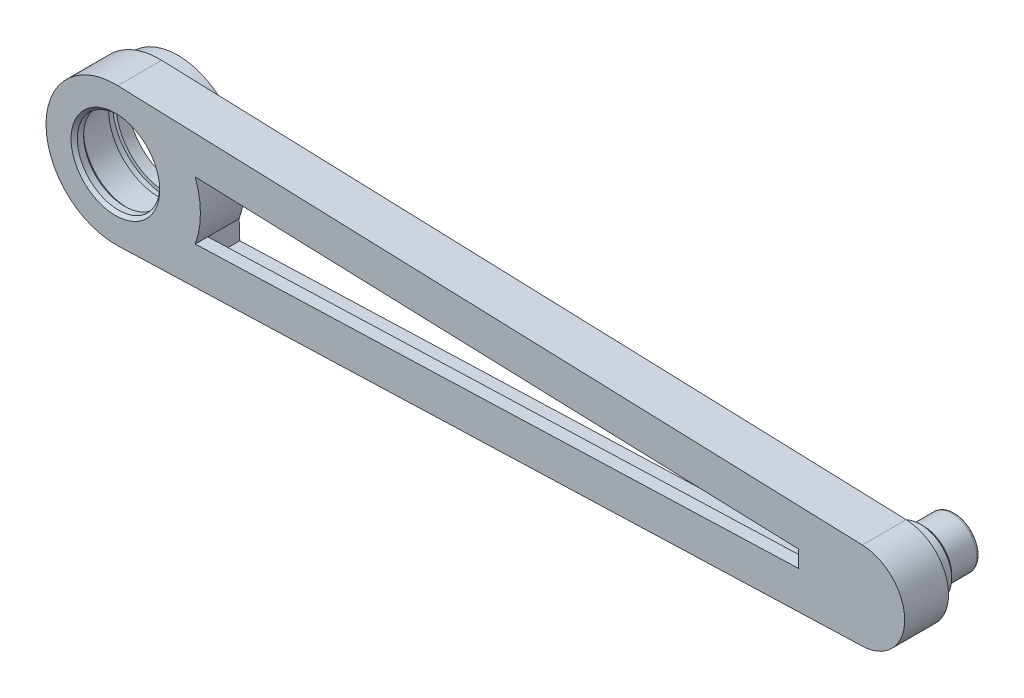
SolidWorks part; units mm, degrees
material "PEI"
ref_plane "前视基准面" through (0, 0, 0) normal (0, 0, 1) x (1, 0, 0)
ref_plane "上视基准面" through (0, 0, 0) normal (0, 1, 0) x (1, 0, 0)
ref_plane "右视基准面" through (0, 0, 0) normal (1, 0, 0) x (0, 0, -1)
other "Configuration Table"
sketch "草图1" plane through (0, 0, 0) normal (0, 0, 1) x (1, 0, 0)
  line L0 (0, 0) -> (119, 0) construction
  line L1 (0.3792, 11.0685) -> (119.2397, 6.9959)
  line L2 (0.3796, -11.0685) -> (119, -7)
  circle A0 centre (119, 0) radius 7
  circle A1 centre (0, 0) radius 8.075
  circle A2 centre (0, 0) radius 11.075
  dimension "D1" = 16.15
  dimension "D3" = 14
  dimension "D2" = 3
  dimension "D4" = 119
extrude "凸台-拉伸1" add sketch "草图1" along normal blind 7 contours A1 A2 | A2 L0 A0 L1 | L0 A2 L2 A0 | A0 region at (7.739, -7.4781, 0) region at (57.6854, 4.654, 0) region at (57.6797, -4.6531, 0) region at (114.2733, 4.8914, 0)
sketch "草图2" plane through (0, 0, 7) normal (0, 0, 1) x (1, 0, 0)
  circle A0 centre (0, 0) radius 8.075 construction
  circle A1 centre (0, 0) radius 8.075
  circle A2 centre (0, 0) radius 6.575
  dimension "D1" = 1.5
extrude "凸台-拉伸2" add sketch "草图2" against normal blind 2
sketch "草图3" plane through (0, 0, 0) normal (0, 0, -1) x (-1, 0, 0)
  arc A0 (-119.2397, 6.9959) -> (-119, -7) centre (-119, 0) ccw construction
  arc A1 (-119.2397, 6.9959) -> (-119, -7) centre (-119, 0) ccw
  circle A2 centre (-119, 0) radius 4
  dimension "D1" = 8
extrude "凸台-拉伸3" add sketch "草图3" along normal blind 10 contours A2 region at (119, 0, 0)
sketch "草图4" plane through (0, 0, 0) normal (0, 0, -1) x (-1, 0, 0)
  circle A0 centre (-119, 0) radius 4 construction
  circle A1 centre (-119, 0) radius 4
  circle A2 centre (-119, 0) radius 5
  dimension "D1" = 1
extrude "凸台-拉伸4" add sketch "草图4" along normal blind 3
chamfer "倒角1" distance 0.5 angle 45 4 edges at (6.575, 0, 7) (6.575, 0, 5) (114, 0, -3) (115, 0, -10)
chamfer "倒角2" [suppressed] distance 1 angle 45
sketch "草图5" plane through (0, 0, 0) normal (0, 0, -1) x (-1, 0, 0)
  line L0 (-0.1738, 5.072) -> (-119.0901, 0.9975)
  line L1 (-118.9996, -0.9965) -> (-0.174, -5.072)
  line L2 (-119, -7) -> (-0.3796, -11.0685)
  line L3 (-119, -7) -> (-0.3796, -11.0685)
  line L8 (-0.3792, 11.0685) -> (-119.2397, 6.9959)
  line L9 (-0.3792, 11.0685) -> (-119.2397, 6.9959)
  arc A0 (-119.0901, 0.9975) -> (-118.9996, -0.9965) centre (-119.0945, -0.0017) ccw
  arc A1 (-0.174, -5.072) -> (-0.1738, 5.072) centre (0, 0) ccw
  arc A2 (-0.3796, -11.0685) -> (-0.3792, 11.0685) centre (0, 0) ccw
  arc A3 (-0.3796, -11.0685) -> (-0.3792, 11.0685) centre (0, 0) ccw
  circle A6 centre (-119, 0) radius 5 construction
  arc A12 (-119.2397, 6.9959) -> (-119, -7) centre (-119, 0) ccw
  arc A13 (-119.2397, 6.9959) -> (-119, -7) centre (-119, 0) ccw
  circle A30 centre (0, 0) radius 8.575
  circle A31 centre (-119, 0) radius 5
  circle A32 centre (-119, 0) radius 10
  circle A33 centre (0, 0) radius 13.575
  dimension "D1" = 0
  dimension "D3" = 5
extrude "切除-拉伸1" cut sketch "草图5" against normal up to surface (7 mm away) contours A33 L0 A32 L1 region at (52.3871, 0.0009, 0) up to face at (7.075, 0, 7)
sketch "草图6" plane through (0, 0, 0) normal (0, 0, -1) x (-1, 0, 0)
  line L0 (-109.0897, -1.3364) -> (-12.7572, -4.6404) construction
  line L1 (-12.7571, 4.6409) -> (-109.0902, 1.3401) construction
  line L2 (-109.0897, -1.3364) -> (-12.7572, -4.6404)
  line L3 (-12.7571, 4.6409) -> (-109.0902, 1.3401)
  line L4 (-12.8598, 7.6391) -> (-109.1929, 4.3384)
  line L5 (-109.1925, -4.3346) -> (-12.8601, -7.6387)
  line L6 (-109.1929, 4.3384) -> (-109.0902, 1.3401)
  line L7 (-109.0897, -1.3364) -> (-109.1925, -4.3346)
  line L8 (-12.8598, 7.6391) -> (-12.7571, 4.6409)
  line L9 (-12.7572, -4.6404) -> (-12.8601, -7.6387)
  dimension "D1" = 3
extrude "切除-拉伸2" cut sketch "草图6" against normal blind 5
sketch "草图7" plane through (0, 0, 0) normal (0, 1, 0) x (1, 0, 0)
  line L0 (122.5, 10) -> (115.5, 10) construction
  line L1 (122.5, 10) -> (115.5, 10)
  line L2 (119, 10) -> (119, 0.7286) construction
  line L4 (115.3, 9) -> (115, 9)
  line L5 (115.3, 9) -> (115.3, 8)
  line L6 (115.3, 8) -> (115, 8)
  line L7 (115, 9) -> (115, 8)
  dimension "D1" = 1
  dimension "D2" = 4
  dimension "D3" = 3.7
  dimension "D4" = 2
revolve "切除-旋转1" [suppressed] cut sketch "草图7" angle 360 about L2
sketch "草图8" plane through (0, 0, -10) normal (0, 0, -1) x (-1, 0, 0)
  circle A0 centre (-119, 0) radius 4 construction
  circle A1 centre (-119, 0) radius 4
extrude "切除-拉伸3" cut sketch "草图8" against normal blind 2
fillet "圆角1" radius 0.5 1 edges at (115, 0, -8)
sketch "草图9" plane through (0, 0, -8) normal (0, 0, -1) x (-1, 0, 0)
  circle A0 centre (-119, 0) radius 2.2
  dimension "D1" = 4.4
extrude "切除-拉伸4" cut sketch "草图9" against normal blind 10
sketch "草图10" plane through (0, 0, 0) normal (0, 0, -1) x (-1, 0, 0)
  circle A0 centre (0, 0) radius 10.075
  circle A1 centre (0, 0) radius 8.075 construction
  circle A2 centre (0, 0) radius 8.075
  dimension "D1" = 2
extrude "凸台-拉伸5" add sketch "草图10" along normal blind 3
sketch "草图11" plane through (0, 0, 0) normal (0, 1, 0) x (1, 0, 0)
  line L0 (8.075, 3) -> (-8.075, 3) construction
  line L1 (5.1574, 1.2) -> (8.65, 1.2)
  line L2 (5.1574, 1.2) -> (5.1574, 0)
  line L3 (5.1574, 0) -> (8.65, 0)
  line L4 (8.65, 1.2) -> (8.65, 0)
  line L5 (0, 0) -> (0, 7.7818) construction
  dimension "D1" = 1.2
  dimension "D2" = 8.65
  dimension "D3" = 3
revolve "切除-旋转2" cut sketch "草图11" angle 360 about L5 region at (6.9037, 0, -0.6)
equation "\"D4@草图1\"= \"连接杆_后_长度\""
equation "\"连接杆_后_长度\"= 119"
